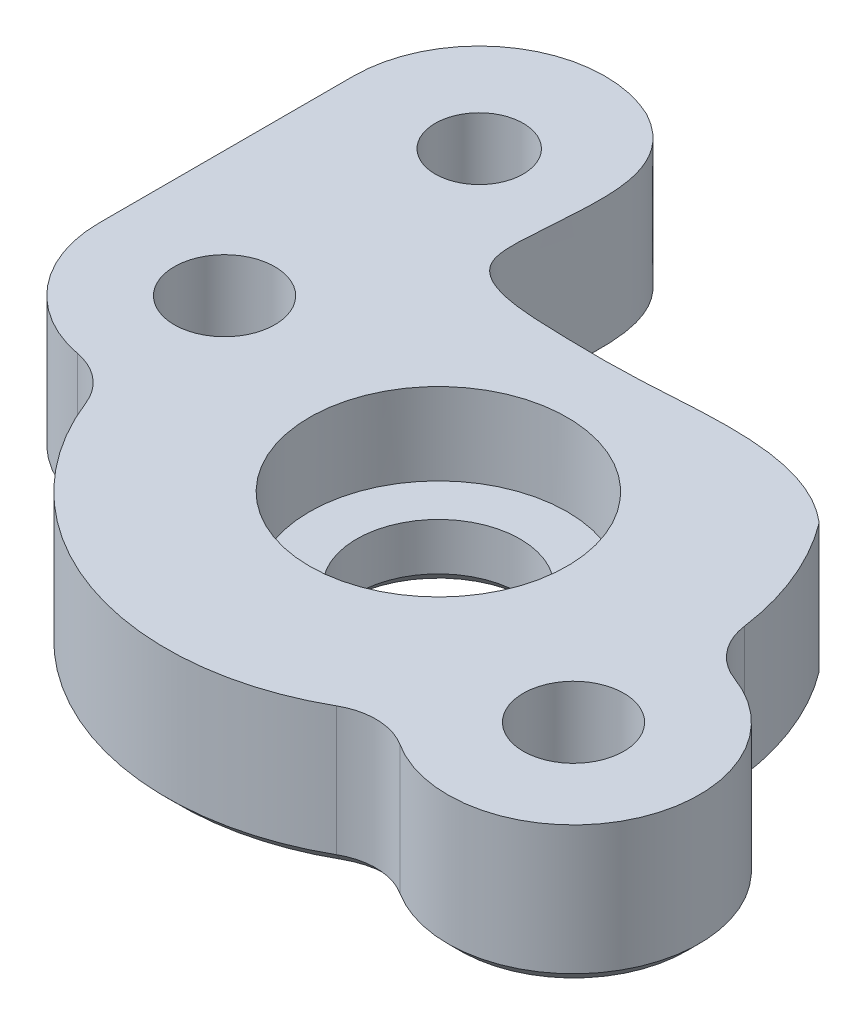
SolidWorks part; units mm, degrees
ref_plane "前视基准面" through (0, 0, 0) normal (0, 0, 1) x (1, 0, 0)
ref_plane "上视基准面" through (0, 0, 0) normal (0, 1, 0) x (1, 0, 0)
ref_plane "右视基准面" through (0, 0, 0) normal (1, 0, 0) x (0, 0, -1)
other "Configuration Table"
sketch "草图1" plane through (0, 0, 0) normal (0, 1, 0) x (1, 0, 0)
  line L1 (0, 0) -> (30, 0)
  line L2 (0, 0) -> (0, 30)
  line L3 (0, 30) -> (30, 30)
  line L4 (30, 0) -> (30, 30)
  dimension "D1" = 30
  dimension "D2" = 30
extrude "凸台-拉伸1" add sketch "草图1" along normal blind 4.5
sketch "草图2" plane through (0, 4.5, 0) normal (0, 1, 0) x (1, 0, 0)
  line L0 (0, 0) -> (30, 0) construction
  line L1 (0, 30) -> (0, 0) construction
  circle A0 centre (21.35, 4.45) radius 1.6
  circle A1 centre (4.05, 10.65) radius 1.6
  circle A2 centre (12.85, 8.65) radius 4.1
  dimension "D1" = 3.2
  dimension "D2" = 3.2
  dimension "D3" = 8.2
  dimension "D4" = 10.65
  dimension "D5" = 4.05
  dimension "D6" = 17.3
  dimension "D7" = 6.2
  dimension "D8" = 8.5
  dimension "D9" = 4.2
  dimension "D10" = 2
  dimension "D11" = 8.8
extrude "切除-拉伸1" cut sketch "草图2" against normal through all
sketch "草图3" plane through (0, 4.5, 0) normal (0, 1, 0) x (1, 0, 0)
  circle A0 centre (4.05, 18.75) radius 1.4
  circle A1 centre (4.05, 10.65) radius 1.6 construction
  dimension "D1" = 2.8
  dimension "D2" = 8.1
  dimension "D3" = 0
extrude "切除-拉伸2" cut sketch "草图3" against normal through all
sketch "草图4" plane through (0, 0, 0) normal (0, -1, 0) x (-1, 0, 0)
  circle A3 centre (-12.85, 8.65) radius 2.6
  circle A5 centre (-12.85, 8.65) radius 4.1
  dimension "D1" = 8.2
  dimension "D2" = 5.2
extrude "凸台-拉伸2" add sketch "草图4" against normal blind 1.9
sketch "草图5" plane through (0, 0, 0) normal (0, -1, 0) x (1, 0, 0)
  line L0 (0.05, -10.65) -> (0.05, -18.75)
  arc A0 (19.7558, -13.8588) -> (21.4976, -8.4473) centre (12.85, -8.65) ccw
  arc A1 (4.4301, -6.6681) -> (0.05, -10.65) centre (4.05, -10.65) ccw
  arc A2 (21.4976, -8.4473) -> (18.2646, -1.9043) centre (21.35, -4.45) ccw
  arc A3 (0.05, -18.75) -> (5.7532, -22.3693) centre (4.05, -18.75) ccw
  arc A4 (18.2646, -1.9043) -> (4.4301, -6.6681) centre (12.85, -8.65) ccw
  spline S0 degree 3 poles (5.7532, -22.3693) (7.856, -21.225) (7.2623, -18.7324) (7.2146, -15.0426) (10.3251, -14.9119) (14.194, -14.8693) (17.852, -15.4712) (19.7558, -13.8588) knots 0 0 0 0 0.297903 0.356444 0.512121 0.640128 1 1 1 1
  dimension "D1" = 17.3
  dimension "D2" = 8
  dimension "D3" = 8
  dimension "D4" = 8
extrude "切除-拉伸3" cut sketch "草图5" against normal through all flip side to cut
fillet "圆角1" radius 2 3 edges at (21.4976, 2.25, -8.4473) (4.4301, 2.25, -6.6681) (18.2646, 2.25, -1.9043)
chamfer "倒角1" distance 0.4 angle 45 14 edges at (1.9067, 0, -22.1273) (0.05, 0, -14.7) (0.9707, 0, -8.097) (4.2134, 0, -6.2947) (9.9703, 0, -0.4934) (18.1698, 0, -1.3938) (24.9361, 0, -2.678) (21.8455, 0, -8.8327) (20.8477, 0, -11.9453) (12.85, 0, -11.25) (4.05, 0, -9.05) (21.35, 0, -2.85) (4.05, 0, -17.35)
equation "\"D1@草图5\"=8.65*2"
